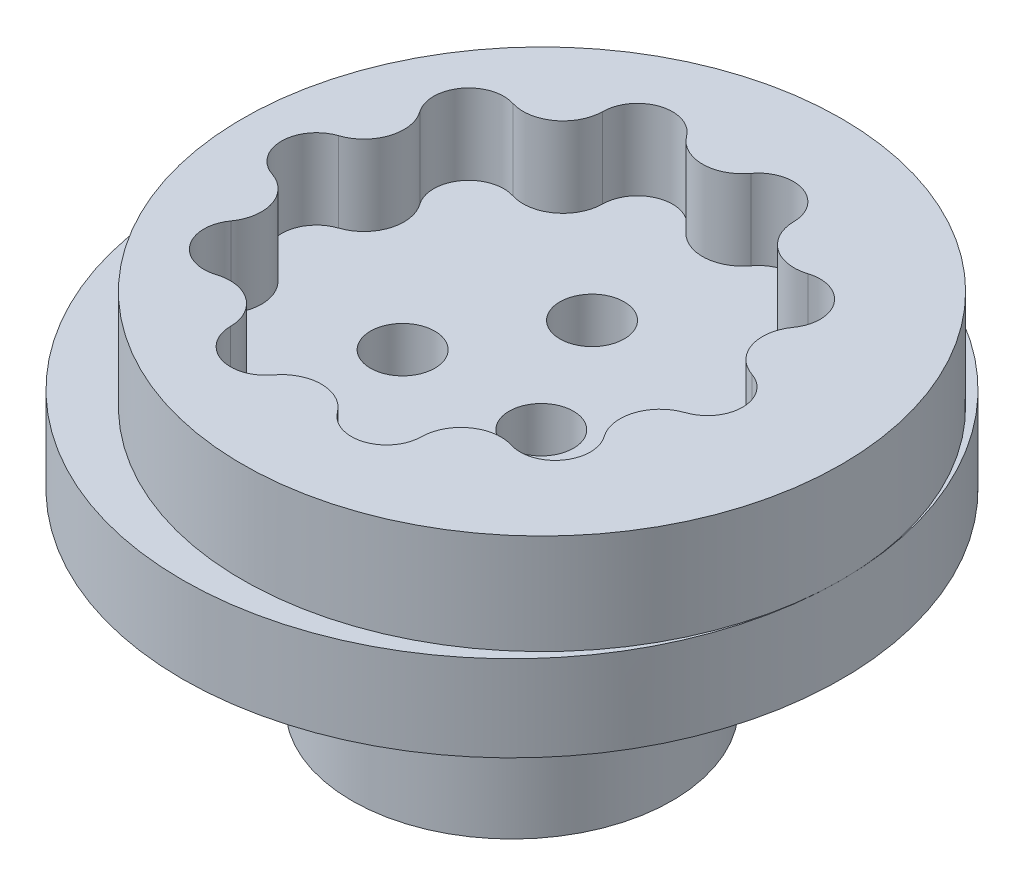
SolidWorks part; units mm, degrees
material "6061 Alloy"
ref_plane "Front" through (0, 0, 0) normal (0, 0, 1) x (1, 0, 0)
ref_plane "Top" through (0, 0, 0) normal (0, 1, 0) x (1, 0, 0)
ref_plane "Right" through (0, 0, 0) normal (1, 0, 0) x (0, 0, -1)
sketch "Sketch1" plane through (0, 0, 0) normal (0, 1, 0) x (1, 0, 0)
  circle A0 centre (0, 0) radius 26.1937 construction
  circle A1 centre (0, 0) radius 26.143
  dimension "D1" = 52.3875
  dimension "D2" = 0.0508
extrude "Boss-Extrude1" add sketch "Sketch1" against normal blind 8.3979
sketch "Sketch2" plane through (0, -8.3979, 0) normal (0, -1, 0) x (1, 0, 0)
  circle A0 centre (0, 0) radius 12.7
  dimension "D1" = 25.4
extrude "Boss-Extrude2" add sketch "Sketch2" along normal blind 15.0812
sketch "Sketch3" plane through (0, 0, 0) normal (0, 1, 0) x (1, 0, 0)
  line L0 (0, 0) -> (0, 26.143) construction
  line L1 (0, 0) -> (15.3664, 21.1501) construction
  arc A0 (2.553, 16.4005) -> (7.5745, 14.7689) centre (4.7912, 14.7457) cw
  circle A2 centre (0, 0) radius 18.288 construction
  arc A3 (0, 15.113) -> (2.553, 16.4005) centre (0, 18.288) ccw
  arc A4 (8.8832, 12.2267) -> (7.5745, 14.7689) centre (10.7494, 14.7953) cw
  arc A5 (8.8832, 12.2267) -> (11.7054, 11.7676) centre (10.7494, 14.7953) ccw
  arc A6 (11.7054, 11.7676) -> (14.8088, 7.4961) centre (12.5434, 9.1133) cw
  arc A7 (14.3733, 4.6702) -> (14.8088, 7.4961) centre (17.3929, 5.6513) cw
  arc A8 (14.3733, 4.6702) -> (16.3867, 2.64) centre (17.3929, 5.6513) ccw
  arc A9 (16.3867, 2.64) -> (16.3867, -2.64) centre (15.5045, 0) cw
  arc A10 (14.3733, -4.6702) -> (16.3867, -2.64) centre (17.3929, -5.6513) cw
  arc A11 (14.3733, -4.6702) -> (14.8088, -7.4961) centre (17.3929, -5.6513) ccw
  arc A12 (14.8088, -7.4961) -> (11.7054, -11.7676) centre (12.5434, -9.1133) cw
  arc A13 (8.8832, -12.2267) -> (11.7054, -11.7676) centre (10.7494, -14.7953) cw
  arc A14 (8.8832, -12.2267) -> (7.5745, -14.7689) centre (10.7494, -14.7953) ccw
  arc A15 (7.5745, -14.7689) -> (2.553, -16.4005) centre (4.7912, -14.7457) cw
  arc A16 (0, -15.113) -> (2.553, -16.4005) centre (0, -18.288) cw
  arc A17 (0, -15.113) -> (-2.553, -16.4005) centre (0, -18.288) ccw
  arc A18 (-2.553, -16.4005) -> (-7.5745, -14.7689) centre (-4.7912, -14.7457) cw
  arc A19 (-8.8832, -12.2267) -> (-7.5745, -14.7689) centre (-10.7494, -14.7953) cw
  arc A20 (-8.8832, -12.2267) -> (-11.7054, -11.7676) centre (-10.7494, -14.7953) ccw
  arc A21 (-11.7054, -11.7676) -> (-14.8088, -7.4961) centre (-12.5434, -9.1133) cw
  arc A22 (-14.3733, -4.6702) -> (-14.8088, -7.4961) centre (-17.3929, -5.6513) cw
  arc A23 (-14.3733, -4.6702) -> (-16.3867, -2.64) centre (-17.3929, -5.6513) ccw
  arc A24 (-16.3867, -2.64) -> (-16.3867, 2.64) centre (-15.5045, 0) cw
  arc A25 (-14.3733, 4.6702) -> (-16.3867, 2.64) centre (-17.3929, 5.6513) cw
  arc A26 (-14.3733, 4.6702) -> (-14.8088, 7.4961) centre (-17.3929, 5.6513) ccw
  arc A27 (-14.8088, 7.4961) -> (-11.7054, 11.7676) centre (-12.5434, 9.1133) cw
  arc A28 (-8.8832, 12.2267) -> (-11.7054, 11.7676) centre (-10.7494, 14.7953) cw
  arc A29 (-8.8832, 12.2267) -> (-7.5745, 14.7689) centre (-10.7494, 14.7953) ccw
  arc A30 (-7.5745, 14.7689) -> (-2.553, 16.4005) centre (-4.7912, 14.7457) cw
  arc A31 (0, 15.113) -> (-2.553, 16.4005) centre (0, 18.288) cw
  circle A32 centre (0, 0) radius 26.143
  circle A33 centre (0, 0) radius 26.143 construction
  point P78 (0, 0)
  dimension "D1" = 36.576
  dimension "D2" = 3.175
  dimension "D3" = 36
extrude "Boss-Extrude3" add sketch "Sketch3" along normal blind 6.35
hole_wizard "1/4-20 Tapped Hole1" positions "Sketch5" profile "Sketch4" tap size "1/4-20" standard "ANSI Inch" end condition through all
sketch "Sketch5" plane through (0, -23.4791, 0) normal (0, -1, 0) x (-1, 0, 0)
  circle A1 centre (0, 0) radius 6.35
  circle A3 centre (0, 0) radius 12.7 construction
  point P2 (0, 6.35)
  point P23 (5.4993, -3.175)
  point P24 (-5.4993, -3.175)
  dimension "D2" = 3
sketch "Sketch4" plane through (0, -23.4791, -6.35) normal (1, 0, 0) x (0, 0, -1)
  line L0 (0, 0) -> (0, 29.8291)
  line L1 (0, 29.8291) -> (2.5527, 29.8291)
  line L2 (2.5527, 29.8291) -> (2.5527, 0)
  line L5 (2.5527, 0) -> (0, 0)
  line L11 (0, -6.35) -> (0, 107.95) construction
  dimension "Thread Major Dia." = 5.1054
  dimension "Thru Tap Drill Depth" = 29.8291
sketch "Sketch6" plane through (0, 6.35, 0) normal (0, 1, 0) x (1, 0, 0)
  line L0 (-26.143, 0) -> (26.143, 0) construction
  line L2 (-33.2518, 33.8083) -> (33.2518, 33.8083)
  line L3 (-33.2518, 33.8083) -> (-33.2518, -33.8083)
  line L4 (-33.2518, -33.8083) -> (33.2518, -33.8083)
  line L5 (33.2518, 33.8083) -> (33.2518, -33.8083)
  line L6 (-33.2518, 33.8083) -> (33.2518, -33.8083) construction
  line L7 (-33.2518, -33.8083) -> (33.2518, 33.8083) construction
  circle A0 centre (0, 0) radius 26.143 construction
  arc A1 (26.143, 0) -> (-21.3805, 0) centre (2.3812, 0) cw
  arc A2 (26.143, 0) -> (-21.3805, 0) centre (2.3812, 0) ccw
  point P7 (0, 0)
  dimension "D1" = 4.7625
extrude "Cut-Extrude2" cut sketch "Sketch6" against normal blind 7.9375
